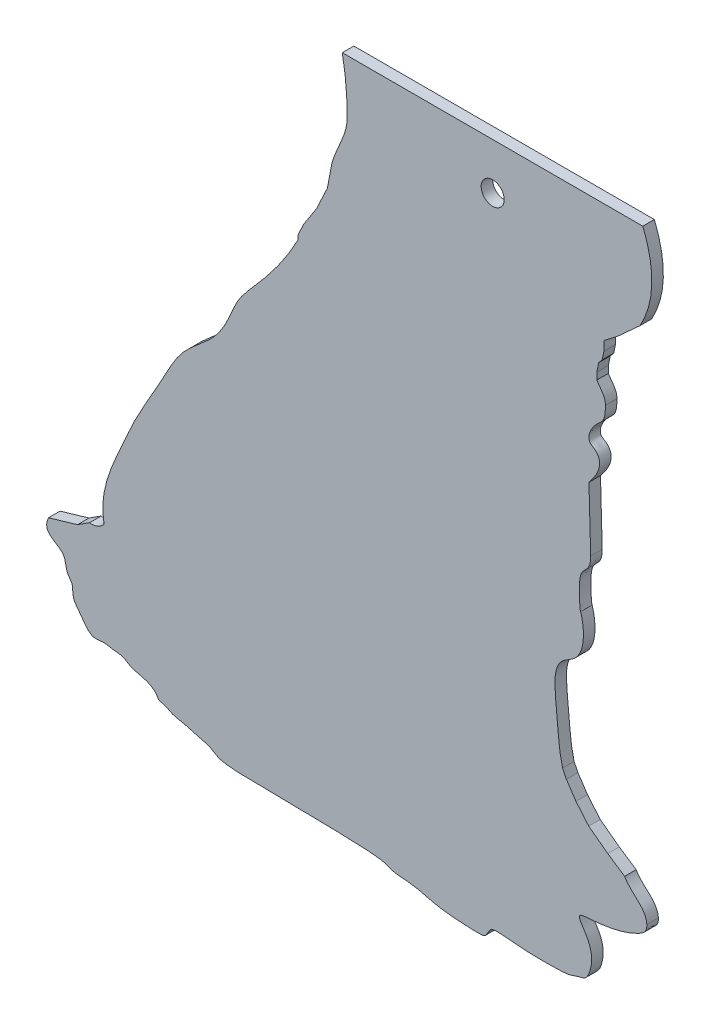
SolidWorks part; units mm, degrees
ref_plane "Front Plane" through (0, 0, 0) normal (0, 0, 1) x (1, 0, 0)
ref_plane "Top Plane" through (0, 0, 0) normal (0, 1, 0) x (1, 0, 0)
ref_plane "Right Plane" through (0, 0, 0) normal (1, 0, 0) x (0, 0, -1)
sketch "Sketch1" plane through (0, 0, 0) normal (0, 0, 1) x (1, 0, 0)
  line L0 (134.6667, 500.5) -> (673.3333, 500.5) construction
  line L2 (167.2022, 42.2012) -> (162.5517, 45.3095)
  line L3 (162.5517, 45.3095) -> (157.3147, 49.2233)
  line L4 (157.3147, 49.2233) -> (153.7929, 53.3936)
  line L5 (153.7929, 53.3936) -> (151.1787, 57.3127)
  line L6 (151.1787, 57.3127) -> (150.1126, 59.4633)
  line L7 (157.3755, 131.2295) -> (157.854, 113.8805)
  line L8 (159.5344, 156.6595) -> (159.5344, 158.498)
  line L9 (159.5344, 158.498) -> (160.0825, 161.1123)
  line L10 (160.0825, 161.1123) -> (161.0243, 162.2425)
  line L11 (161.0243, 162.2425) -> (161.5128, 164.5724)
  line L12 (161.5128, 164.5724) -> (161.5128, 167.1023)
  line L13 (161.5128, 167.1023) -> (165.1835, 169.9013)
  line L14 (165.1835, 169.9013) -> (171.472, 175.6217)
  line L15 (86.5908, 171.7678) -> (85.3882, 165.3811)
  line L16 (89.473, 199.6877) -> (172.1964, 199.6877)
  line L17 (85.3882, 165.3811) -> (82.4023, 158.9826)
  line L18 (82.4023, 158.9826) -> (78.8266, 153.4325)
  line L19 (78.8266, 153.4325) -> (77.3096, 150.1819)
  line L20 (77.3096, 150.1819) -> (77.3096, 148.973)
  line L21 (89.473, 199.6877) -> (189.494, 199.6877) construction
  line L22 (127.4919, 8.5553) -> (214.3131, 8.5553) construction
  line L23 (8.6124, 48.3831) -> (8.6124, -14.4171) construction
  line L24 (173.32, 33.793) -> (173.32, -11.6797) construction
  circle A0 centre (130.8722, 186.9242) radius 3.175
  spline S0 degree 1 poles (8.6124, 48.3831) (16.6111, 50.7357) knots 0 0 1 1
  spline S1 degree 1 poles (19.9047, 52.853) (16.6111, 50.7357) knots 0 0 1 1
  spline S2 degree 3 poles (23.9041, 54.4997) (22.542, 62.0444) (27.1512, 71.7199) (33.1716, 85.6736) (39.4703, 95.7444) (45.0444, 107.3971) (54.1548, 113.0729) (58.3579, 120.6747) (60.6418, 126.7915) (68.4166, 135.2748) (73.9208, 142.4894) (77.3096, 148.973) knots 0 0 0 0 0.194457 0.285904 0.412664 0.517827 0.629269 0.691339 0.750377 0.804905 1 1 1 1
  spline S3 degree 2 poles (19.9047, 52.853) (22.4371, 52.6083) (23.9041, 54.4997) knots 0 0 0 1 1 1
  spline S4 degree 3 poles (8.6124, 48.3831) (6.5691, 43.9628) (13.6478, 43.7296) (13.2535, 37.9915) (15.2259, 36.1128) (15.2445, 34.2074) (15.4257, 32.4092) (16.9812, 30.3171) (18.455, 28.2086) (20.7273, 25.6089) (23.6404, 26.5196) (26.3788, 25.705) (29.0077, 25.795) (31.226, 24.0079) (34.9468, 23.3493) (38.0007, 22.2222) (38.8831, 20.145) knots 0 0 0 0 0.18572 0.273851 0.320038 0.350192 0.393849 0.435551 0.514834 0.569195 0.638874 0.687587 0.755837 0.801068 0.865551 1 1 1 1
  spline S5 degree 3 poles (38.8831, 20.145) (41.2875, 19.5656) (42.3458, 18.5073) (45.4199, 18.1546) (49.7538, 16.7939) (52.7775, 16.1892) (54.7934, 14.8285) (56.3556, 14.1734) (60.1352, 13.7702) (61.5463, 13.7702) (99.2418, 13.2159) (101.2856, 12.2232) (103.9594, 11.2977) (106.3246, 11.2977) (111.5693, 10.5778) (115.1686, 9.2409) (123.9098, 8.5211) (128.0233, 8.5211) (128.9488, 8.7267) (129.9772, 10.7835) (131.0055, 11.8119) (139.3353, 10.7835) (144.7857, 10.7835) (151.9843, 10.7835) (154.3496, 12.1204) (156.7148, 12.1204) (158.1545, 16.0282) (158.1545, 19.319) (157.3318, 21.6842) (156.4063, 23.3296) (153.7325, 27.1346) (157.3189, 27.1346) (163.0629, 27.7755) (167.4392, 28.9243) (170.3933, 30.1004) (172.4447, 31.2857) (173.2037, 32.3228) (173.32, 33.1913) (173.32, 33.793) knots 0 0 0 0 0.028571 0.057143 0.085714 0.114286 0.142857 0.171429 0.2 0.228571 0.257143 0.285714 0.314286 0.342857 0.371429 0.4 0.428571 0.457143 0.485714 0.514286 0.542857 0.571429 0.6 0.628571 0.657143 0.685714 0.714286 0.742857 0.771429 0.8 0.828571 0.857143 0.885714 0.914286 0.942857 0.971429 0.985714 1 1 1 1
  spline S6 degree 3 poles (173.32, 33.793) (173.0564, 37.6266) (168.8406, 39.1122) (167.2022, 42.2012) knots 0 0 0 0 1 1 1 1
  spline S7 degree 3 poles (150.1126, 59.4633) (148.9568, 63.837) (148.9486, 71.4394) (146.8505, 84.0514) (156.4694, 88.1502) (156.2475, 95.5102) (155.0853, 99.2556) knots 0 0 0 0 0.308783 0.618237 0.704406 1 1 1 1
  spline S8 degree 3 poles (157.854, 113.8805) (157.8564, 113.8699) (157.8506, 110.688) (155.3081, 109.3846) (154.4188, 105.0533) (154.8696, 99.4834) (155.0853, 99.2556) knots 0 0 0 0 0.124799 0.365608 0.555267 1 1 1 1
  spline S9 degree 3 poles (161.8927, 151.8072) (161.9125, 149.0313) (161.4499, 147.7916) (158.4451, 145.386) (156.1309, 141.3803) (158.8302, 140.0435) (161.6487, 137.4079) (159.4597, 133.7277) (157.3755, 131.2295) knots 0 0 0 0 0.190659 0.228613 0.488803 0.534056 0.585176 1 1 1 1
  spline S10 degree 3 poles (159.5344, 156.6595) (160.7867, 154.8399) (162.0055, 153.6124) (161.8927, 151.8072) knots 0 0 0 0 1 1 1 1
  spline S11 degree 2 poles (172.1964, 199.6877) (177.5125, 186.6119) (171.472, 175.6217) knots 0 0 0 1 1 1
  spline S12 degree 3 poles (89.473, 199.6877) (90.4497, 194.8375) (90.826, 189.8378) (90.8383, 180.2807) (87.6783, 176.1914) (86.5908, 171.7678) knots 0 0 0 0 0.517811 0.520823 1 1 1 1
  point P123 (0, 0)
  point P124 (130.8722, 186.9242)
  dimension "D1" = 191.1324
  dimension "D2" = 164.7075
extrude "Boss-Extrude2" add sketch "Sketch1" along normal blind 3.175
